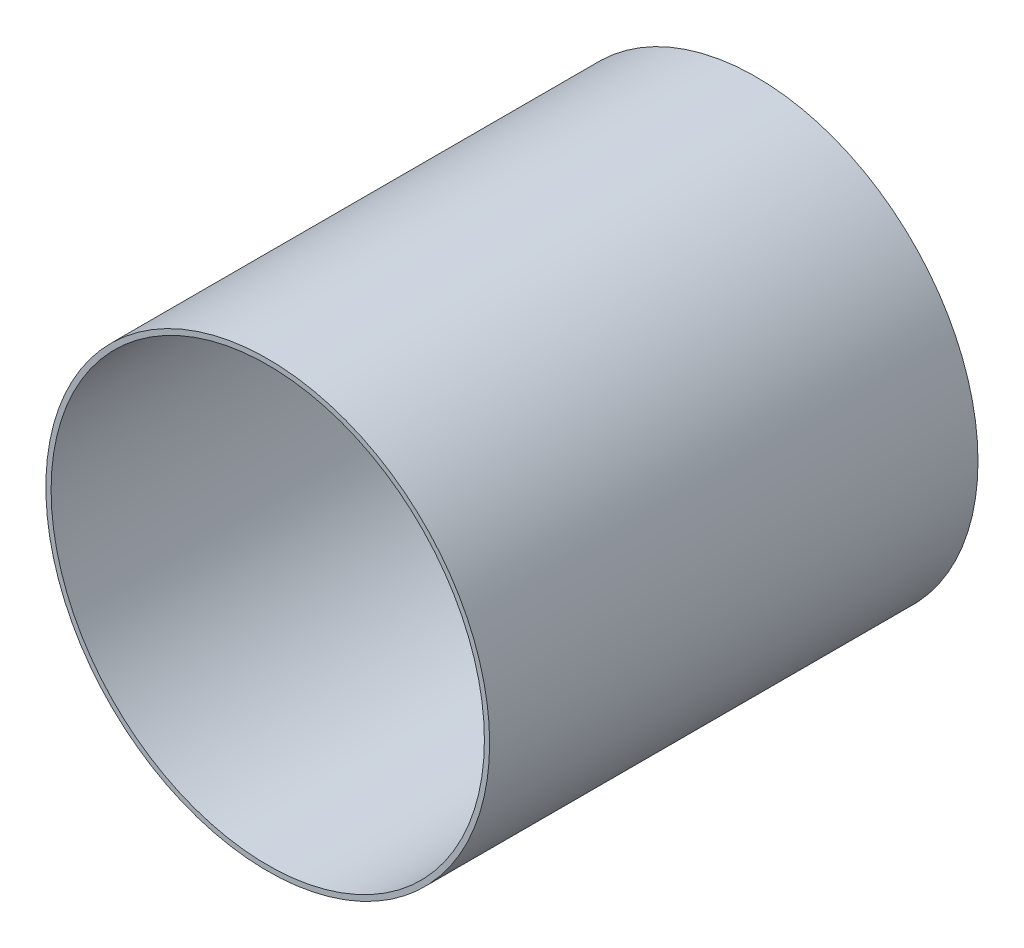
SolidWorks part; units mm, degrees
ref_plane "Front Plane" through (0, 0, 0) normal (0, 0, 1) x (1, 0, 0)
ref_plane "Top Plane" through (0, 0, 0) normal (0, 1, 0) x (1, 0, 0)
ref_plane "Right Plane" through (0, 0, 0) normal (1, 0, 0) x (0, 0, -1)
sketch "Sketch1" plane through (0, 0, 0) normal (0, 0, 1) x (1, 0, 0)
  circle A0 centre (0, 0) radius 63.4746
  circle A1 centre (0, 0) radius 61.976
  dimension "D1" = 123.952
  dimension "D2" = 126.9492
extrude "Boss-Extrude1" add sketch "Sketch1" along normal mid plane 139.7
equation "\"AIRFRAME_OD\"= 5.15in"
equation "\"AIRFRAME_ID\"= 5.00in"
equation "\"FLAT_T\"= 0.125in"
equation "\"NOSE_EXP_L\"= 27in"
equation "\"NOSE_SHOULDER_L\"= 5in"
equation "\"MAIN_L\"= 30in"
equation "\"RECO_COUP_L\"= 10in"
equation "\"RECO_SWITCH_L\"= 2in"
equation "\"DROGUE_L\"= 20in"
equation "\"ATS_FORE_COUP_L\"= 5.5in"
equation "\"ATS_AFT_COUP_L\"= 4.5in"
equation "\"LOWER_L\"= 30in"
equation "\"FIN_N\"= 4"
equation "\"CR_AFT_X\"= 0.5in"
equation "\"CR_FORE_X\"= 9.25in"
equation "\"D1@Sketch1\"=\"COUPLER_ID\""
equation "\"D2@Sketch1\"=\"COUPLER_OD\""
equation "\"D1@Boss-Extrude1\"=\"ATS_FORE_COUP_L\""
equation "\"FIN_ROOT\"= 8in"
equation "\"FIN_X\"= 0.75in"
equation "\"MOTOR_OD\"= 3.091in"
equation "\"MOTOR_ID\"= 3.00in"
equation "\"COUPLER_OD\"= 4.998in"
equation "\"COUPLER_ID\"= 4.88in"
equation "\"RECO_ROD_X\"= 3.5in"
equation "\"ATS_ROD_X\"= 3in"
equation "\"MOTOR_L\"= 14in"
equation "\"MOTOR_LOWER_X\"= 2in"
